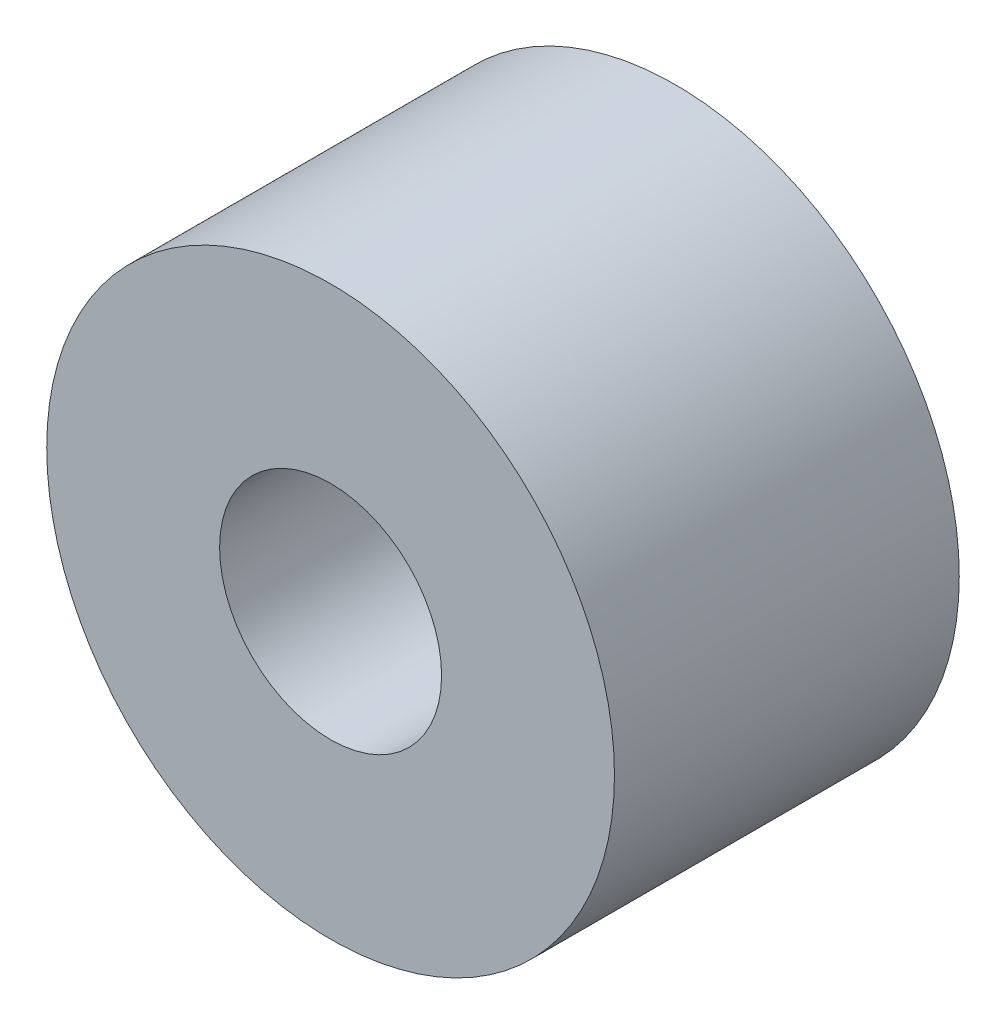
SolidWorks part; units mm, degrees
ref_plane "Front Plane" through (0, 0, 0) normal (0, 0, 1) x (1, 0, 0)
ref_plane "Top Plane" through (0, 0, 0) normal (0, 1, 0) x (1, 0, 0)
ref_plane "Right Plane" through (0, 0, 0) normal (1, 0, 0) x (0, 0, -1)
sketch "Sketch1" plane through (0, 0, 0) normal (0, 0, 1) x (1, 0, 0)
  circle A0 centre (0, 0) radius 4.775
  circle A1 centre (0, 0) radius 1.8669
  dimension "D1" = 9.55
  dimension "D2" = 3.7338
extrude "Boss-Extrude1" add sketch "Sketch1" along normal blind 5.8
